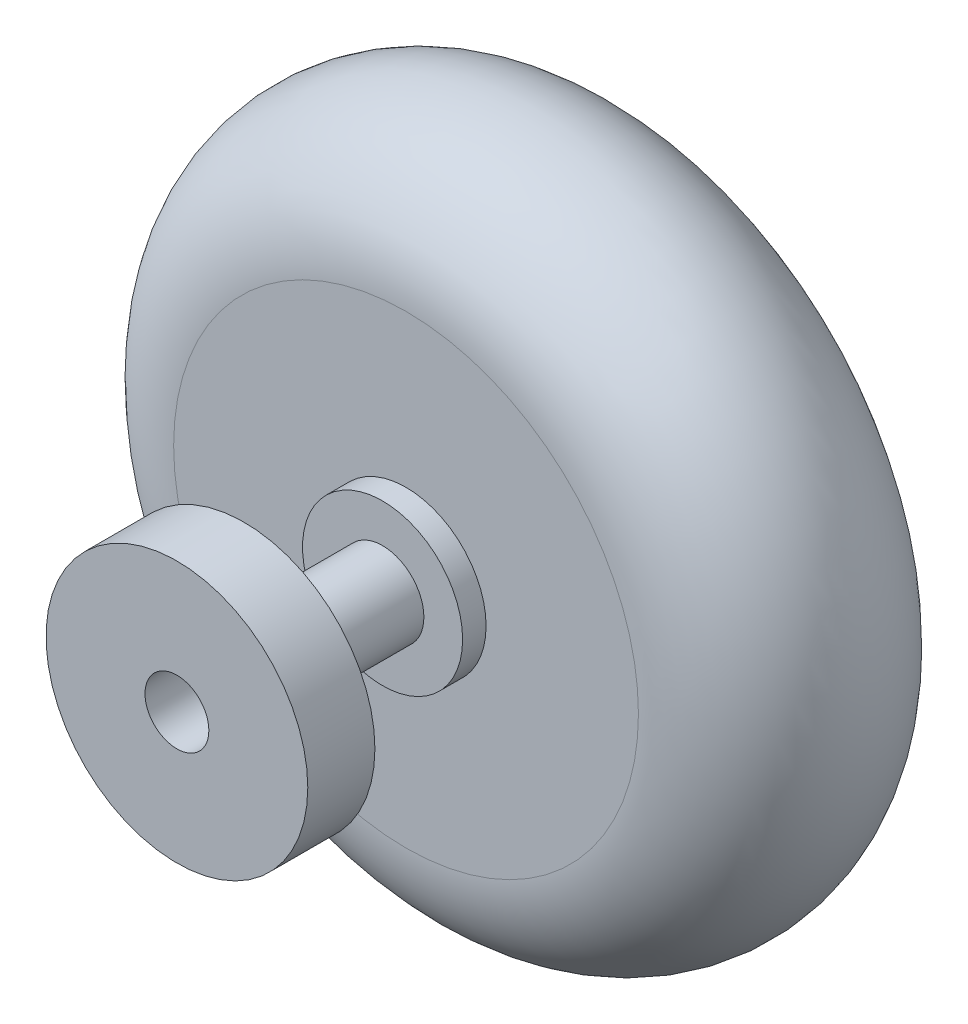
SolidWorks part; units mm, degrees
material "ABS"
ref_plane "Front Plane" through (0, 0, 0) normal (0, 0, 1) x (1, 0, 0)
ref_plane "Top Plane" through (0, 0, 0) normal (0, 1, 0) x (1, 0, 0)
ref_plane "Right Plane" through (0, 0, 0) normal (1, 0, 0) x (0, 0, -1)
sketch "Sketch1" plane through (0, 0, 0) normal (0, 0, 1) x (1, 0, 0)
  circle A0 centre (0, 0) radius 14.9
  dimension "D1" = 29.8
extrude "Boss-Extrude1" add sketch "Sketch1" against normal blind 10
fillet "Fillet1" 2 edges at (14.9, 0, -10) (14.9, 0, 0) type full round first side face at (14.9, 0, -10) second side face at (14.9, 0, 0) middle face at (14.9, 0, -10)
sketch "Sketch3" plane through (0, 0, 0) normal (0, 0, 1) x (1, 0, 0)
  circle A0 centre (0, 0) radius 3.41
  dimension "D1" = 6.82
extrude "Boss-Extrude2" add sketch "Sketch3" along normal blind 1
sketch "Sketch4" plane through (0, 0, 1) normal (0, 0, 1) x (1, 0, 0)
  circle A0 centre (0, 0) radius 1.76
  dimension "D1" = 3.52
extrude "Boss-Extrude3" add sketch "Sketch4" along normal blind 5.9
sketch "Sketch5" plane through (0, 0, 6.9) normal (0, 0, 1) x (1, 0, 0)
  circle A0 centre (0, 0) radius 5.575
  dimension "D1" = 11.15
extrude "Boss-Extrude4" add sketch "Sketch5" along normal blind 2.86
sketch "Sketch6" plane through (0, 0, 9.76) normal (0, 0, 1) x (1, 0, 0)
  circle A0 centre (0, 0) radius 1.36
  dimension "D1" = 2.72
extrude "Cut-Extrude1" cut sketch "Sketch6" against normal blind 2.86
sketch "Sketch7" plane through (0, 0, -10) normal (0, 0, -1) x (-1, 0, 0)
  circle A0 centre (0, 0) radius 3.405
  dimension "D1" = 6.81
extrude "Boss-Extrude5" add sketch "Sketch7" along normal blind 0.5
sketch "Sketch8" plane through (0, 0, -10.5) normal (0, 0, -1) x (-1, 0, 0)
  circle A0 centre (0, 0) radius 1.79
  dimension "D1" = 3.58
extrude "Boss-Extrude6" add sketch "Sketch8" along normal blind 1.92
sketch "Sketch9" plane through (0, 0, -12.42) normal (0, 0, -1) x (-1, 0, 0)
  circle A0 centre (0, 0) radius 2.85
  dimension "D1" = 5.7
extrude "Boss-Extrude7" add sketch "Sketch9" along normal blind 1.12
sketch "Sketch10" plane through (0, 0, -13.54) normal (0, 0, -1) x (-1, 0, 0)
  circle A0 centre (0, 0) radius 1.11
  dimension "D1" = 2.22
extrude "Boss-Extrude8" add sketch "Sketch10" along normal blind 1.5 draft 5
sketch "Sketch11" plane through (0, 0, -15.04) normal (0, 0, -1) x (-1, 0, 0)
  circle A0 centre (0, 0) radius 0.76
  dimension "D1" = 1.52
extrude "Boss-Extrude9" add sketch "Sketch11" along normal blind 2.24
